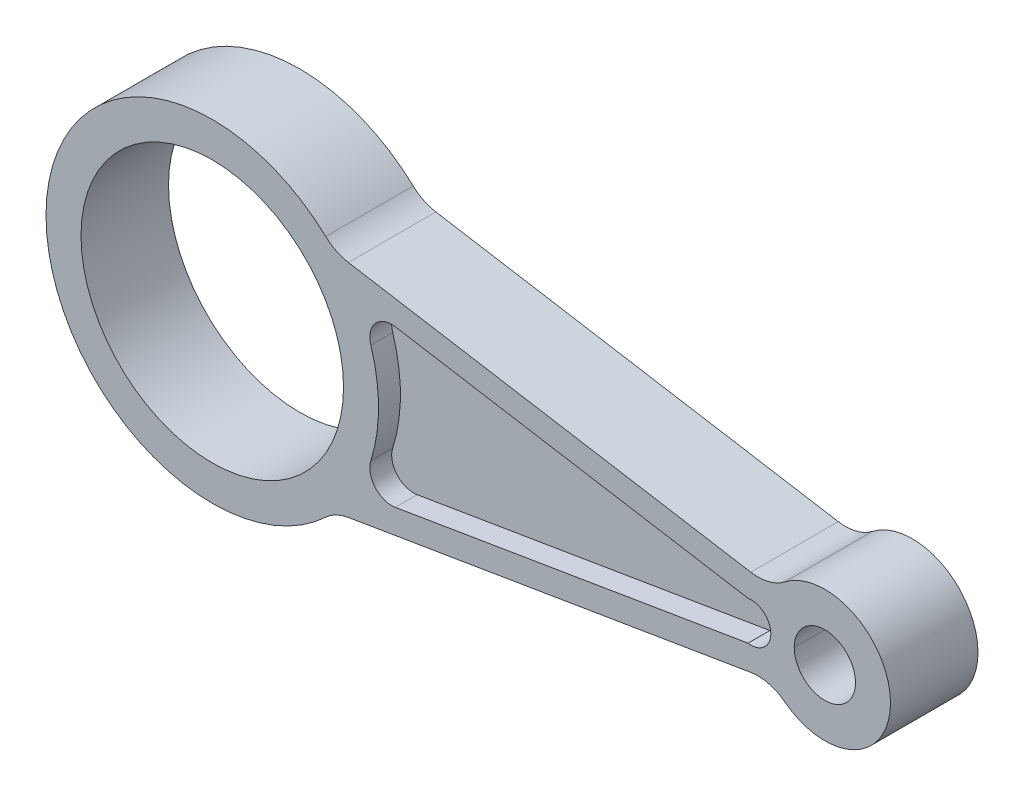
SolidWorks part; units mm, degrees
material "Plain Carbon Steel"
ref_plane "Front Plane" through (0, 0, 0) normal (0, 0, 1) x (1, 0, 0)
ref_plane "Top Plane" through (0, 0, 0) normal (0, 1, 0) x (1, 0, 0)
ref_plane "Right Plane" through (0, 0, 0) normal (1, 0, 0) x (0, 0, -1)
sketch "Sketch1" plane through (0, 0, 0) normal (0, 0, 1) x (1, 0, 0)
  line L0 (0, 0) -> (140, 0) construction
  line L1 (128.0638, 9.0844) -> (27.9355, 25.7606)
  line L2 (27.9355, -25.7606) -> (128.0638, -9.0844)
  circle A0 centre (0, 0) radius 30
  circle A1 centre (140, 0) radius 7
  arc A2 (27.9355, 25.7606) -> (27.9355, -25.7606) centre (0, 0) ccw
  arc A3 (128.0638, -9.0844) -> (128.0638, 9.0844) centre (140, 0) ccw
  arc A4 (38, 0) -> (27.9355, 25.7606) centre (0, 0) ccw construction
  arc A5 (27.9355, -25.7606) -> (38, 0) centre (0, 0) ccw construction
  arc A6 (128.0638, 9.0844) -> (125, 0) centre (140, 0) ccw construction
  arc A7 (125, 0) -> (128.0638, -9.0844) centre (140, 0) ccw construction
  dimension "D1" = 60
  dimension "D2" = 14
  dimension "D3" = 76
  dimension "D4" = 30
  dimension "D5" = 140
extrude "Boss-Extrude1" add sketch "Sketch1" along normal mid plane 20
fillet "Fillet1" radius 10 1 edges at (27.9355, 25.7606, 0)
fillet "Fillet2" radius 10 1 edges at (27.9355, -25.7606, 0)
fillet "Fillet3" radius 10 1 edges at (128.0638, 9.0844, 0)
fillet "Fillet4" radius 10 1 edges at (128.0638, -9.0844, 0)
sketch "Sketch2" plane through (0, 0, 10) normal (0, 0, 1) x (1, 0, 0)
  line L0 (0, 0) -> (140, 0) construction
  line L1 (41.8286, 17.871) -> (122.4444, 4.4445)
  line L2 (41.8286, -17.871) -> (122.4444, -4.4445)
  line L3 (123.0688, 9.9163) -> (31.1011, 25.2334) construction
  line L4 (31.1011, -25.2334) -> (123.0688, -9.9163) construction
  arc A0 (122.4444, -4.4445) -> (122.4444, 4.4445) centre (123.1488, 0) ccw
  arc A1 (41.8286, 17.871) -> (36.2389, 11.4344) centre (41.0071, 12.9389) ccw
  arc A2 (36.2389, 11.4344) -> (36.2389, -11.4344) centre (0, 0) cw
  arc A3 (36.2389, -11.4344) -> (41.8286, -17.871) centre (41.0071, -12.9389) ccw
  circle A4 centre (0, 0) radius 30 construction
  point P16 (43.4664, -9.0135)
  point P18 (10.4355, -4.1094)
  point P19 (0, 0)
  dimension "D3" = 4.5
  dimension "D4" = 5
  dimension "D5" = 8
  dimension "D1" = 5.5
  dimension "D2" = 5.5
extrude "Cut-Extrude1" cut sketch "Sketch2" against normal blind 5
mirror "Mirror1" about plane through (0, 0, 0) normal (0, 0, 1) of "Cut-Extrude1"
split line "Split Line1"
